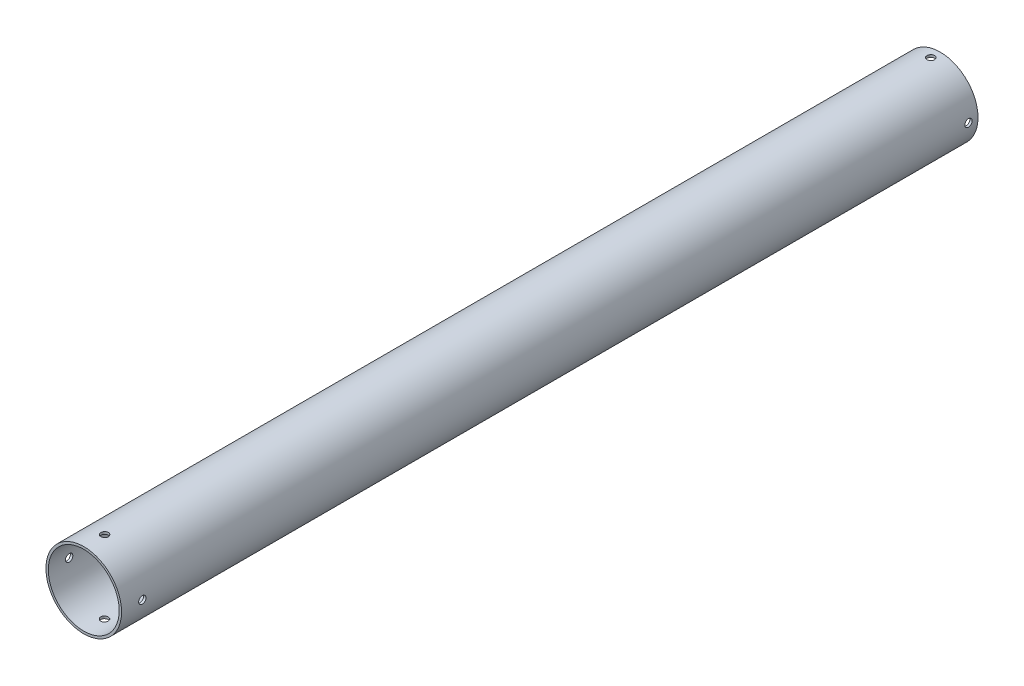
SolidWorks part; units mm, degrees
material "PC High Viscosity"
ref_plane "Front Plane" through (0, 0, 0) normal (0, 0, 1) x (1, 0, 0)
ref_plane "Top Plane" through (0, 0, 0) normal (0, 1, 0) x (1, 0, 0)
ref_plane "Right Plane" through (0, 0, 0) normal (1, 0, 0) x (0, 0, -1)
sketch "Sketch1" plane through (0, 0, 0) normal (0, 0, 1) x (1, 0, 0)
  circle A0 centre (0, 0) radius 23.8125
  circle A1 centre (0, 0) radius 25.4
  dimension "D1" = 50.8
  dimension "D2" = 47.625
extrude "Boss-Extrude1" add sketch "Sketch1" along normal mid plane 575.213
sketch "Sketch2" plane through (0, 0, 0) normal (1, 0, 0) x (0, 0, -1)
  line L0 (287.6065, -25.4) -> (287.6065, 25.4) construction
  circle A0 centre (281.2565, 0) radius 2.4892
  dimension "D1" = 6.35
  dimension "D2" = 4.9784
extrude "Cut-Extrude1" cut sketch "Sketch2" against normal through all both and the other way through all
sketch "Sketch3" plane through (0, 0, 0) normal (0, 1, 0) x (1, 0, 0)
  line L0 (25.4, 287.6065) -> (-25.4, 287.6065) construction
  circle A0 centre (0, 281.2565) radius 2.4892
  dimension "D1" = 4.9784
  dimension "D2" = 6.35
extrude "Cut-Extrude2" cut sketch "Sketch3" against normal through all both and the other way through all
sketch "Sketch4" plane through (0, 0, 0) normal (0, 1, 0) x (1, 0, 0)
  line L0 (-25.4, -287.6065) -> (25.4, -287.6065) construction
  circle A0 centre (0, -273.6365) radius 2.4892
  point P4 (0, 0)
  dimension "D1" = 4.9784
  dimension "D2" = 13.97
extrude "Cut-Extrude3" cut sketch "Sketch4" against normal through all both and the other way through all
sketch "Sketch5" plane through (0, 0, 0) normal (1, 0, 0) x (0, 0, -1)
  line L0 (-287.6065, 25.4) -> (-287.6065, -25.4) construction
  circle A0 centre (-273.6365, 0) radius 2.4892
  point P4 (0, 0)
  dimension "D1" = 4.9784
  dimension "D2" = 13.97
extrude "Cut-Extrude4" cut sketch "Sketch5" against normal through all both and the other way through all
equation "\"D1@Boss-Extrude1\"=21.125in+3.625mm"
